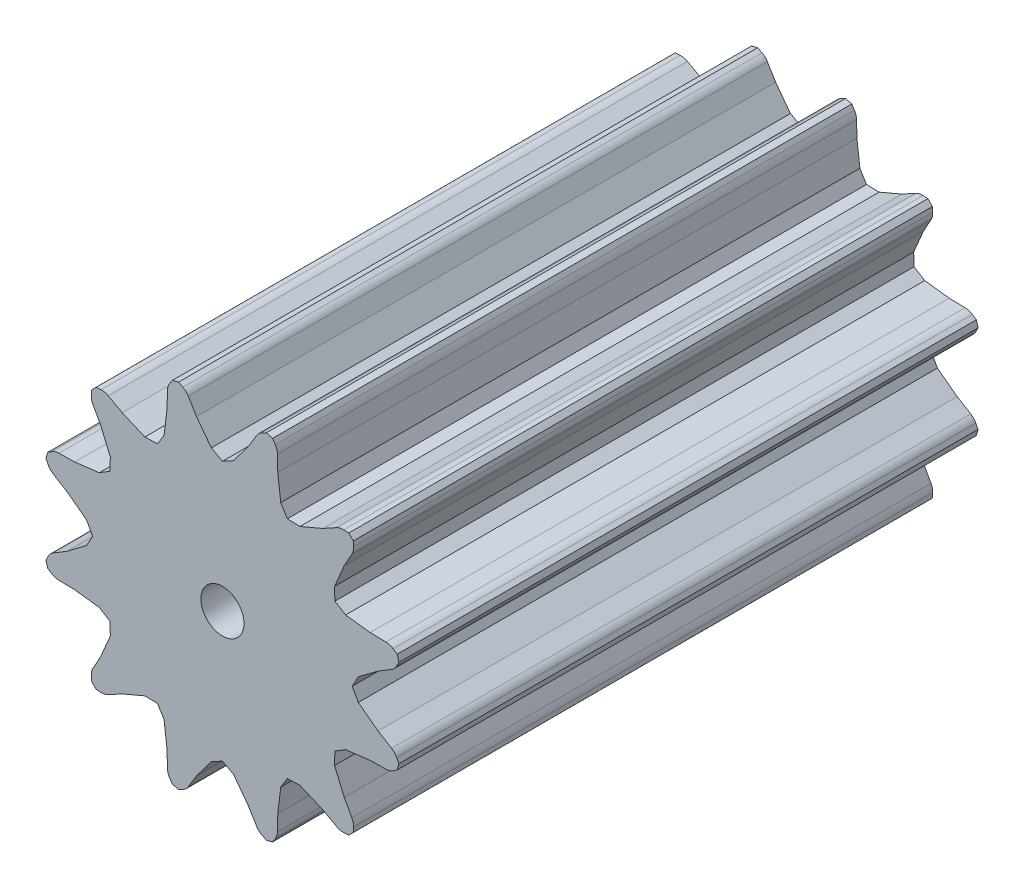
SolidWorks part; units mm, degrees
ref_plane "Front Plane" through (0, 0, 0) normal (0, 0, 1) x (1, 0, 0)
ref_plane "Top Plane" through (0, 0, 0) normal (0, 1, 0) x (1, 0, 0)
ref_plane "Right Plane" through (0, 0, 0) normal (1, 0, 0) x (0, 0, -1)
sketch "Sketch1" plane through (0, 0, 0) normal (0, 0, 1) x (1, 0, 0)
  line L1 (1.2374, -1.2374) -> (-1.2374, -1.2374) construction
  line L2 (1.2374, -1.2374) -> (1.2374, 1.2374) construction
  line L3 (1.2374, 1.2374) -> (-1.2374, 1.2374) construction
  line L4 (-1.2374, -1.2374) -> (-1.2374, 1.2374) construction
  line L5 (1.2374, -1.2374) -> (-1.2374, 1.2374) construction
  line L6 (1.2374, 1.2374) -> (-1.2374, -1.2374) construction
  circle A0 centre (0, 0) radius 13.5
  circle A1 centre (0, 0) radius 1.75 construction
  dimension "D1" = 27
  dimension "D2" = 3.5
extrude "Boss-Extrude1" add sketch "Sketch1" along normal blind 43
sketch "Sketch2" plane through (0, 0, 0) normal (0, 0, 1) x (1, 0, 0)
  line L0 (0, 0) -> (0, 10.088) construction
  line L1 (0, 9.6396) -> (-0.8235, 10.088)
  line L8 (-3.2618, 13.1) -> (0, 19.2384)
  line L11 (-0.8235, 10.088) -> (-1.925, 11.5528)
  line L12 (-1.925, 11.5528) -> (-2.6827, 12.8069)
  line L13 (-2.6827, 12.8069) -> (-3.2618, 13.1)
  line L14 (2.6827, 12.8069) -> (3.2618, 13.1)
  line L15 (1.925, 11.5528) -> (2.6827, 12.8069)
  line L16 (0.8235, 10.088) -> (1.925, 11.5528)
  line L17 (3.2618, 13.1) -> (0, 19.2384)
  line L18 (0, 9.6396) -> (0.8235, 10.088)
  circle A14 centre (0, 0) radius 13.5 construction
  point P4 (-4.0099, 17.5282)
  point P16 (0, 13.5)
  point P17 (0, 19.2384)
  point P18 (0, 7.8209)
  point P19 (-0.8117, 8.2417)
  point P20 (-2.074, 9.2515)
  point P21 (-4.0099, 14.4541)
  point P22 (0, 9.6396)
  point P23 (-0.8235, 10.088)
  point P24 (-1.925, 11.5528)
  point P25 (-3.0397, 14.6888)
  point P26 (-2.3793, 13.9754)
  point P27 (-2.9372, 14.7096)
  point P28 (-2.7302, 13.9509)
  point P29 (-3.3486, 14.6215)
  point P30 (2.5601, 12.8346)
  point P31 (-2.6827, 12.8069)
  point P32 (-3.2618, 13.1)
extrude "Cut-Extrude1" cut sketch "Sketch2" along normal through all
pattern_circular "CirPattern1" count 12 over 360 about axis through (0, 0, 43) along (0, 0, -1) of "Cut-Extrude1" reverse direction yes
sketch "Sketch3" plane through (0, 0, 0) normal (0, 0, 1) x (1, 0, 0)
  circle A0 centre (0, 0) radius 7.5
  dimension "D1" = 15
sketch "Sketch4" plane through (0, 0, 43) normal (0, 0, 1) x (1, 0, 0)
  circle A0 centre (0, 0) radius 1.6
  dimension "D1" = 3.2
fillet "Fillet1" radius 1 24 edges at (-8.7267, 9.7498, 21.5) (-9.7498, 8.7267, 21.5) (-12.4325, 4.0802, 21.5) (-12.8069, 2.6827, 21.5) (-12.8069, -2.6827, 21.5) (-12.4325, -4.0802, 21.5) (-9.7498, -8.7267, 21.5) (-8.7267, -9.7498, 21.5) (-4.0802, -12.4325, 21.5) (-2.6827, -12.8069, 21.5) (2.6827, -12.8069, 21.5) (4.0802, -12.4325, 21.5) (8.7267, -9.7498, 21.5) (12.4325, -4.0802, 21.5) (9.7498, -8.7267, 21.5) (12.8069, -2.6827, 21.5) (12.8069, 2.6827, 21.5) (12.4325, 4.0802, 21.5) (9.7498, 8.7267, 21.5) (4.0802, 12.4325, 21.5) (8.7267, 9.7498, 21.5) (2.6827, 12.8069, 21.5) (-2.6827, 12.8069, 21.5) (-4.0802, 12.4325, 21.5)
extrude "Cut-Extrude2" cut sketch "Sketch4" against normal through all both and the other way through all
equation "\"circle\"=27"
equation "\"D1@Sketch1\"=\"circle\""
equation "\"separator_width\"=45"
equation "\"big-gear-thiccness\"=2"
equation "\"D1@Boss-Extrude1\"=\"separator_width\" - \"big-gear-thiccness\""
